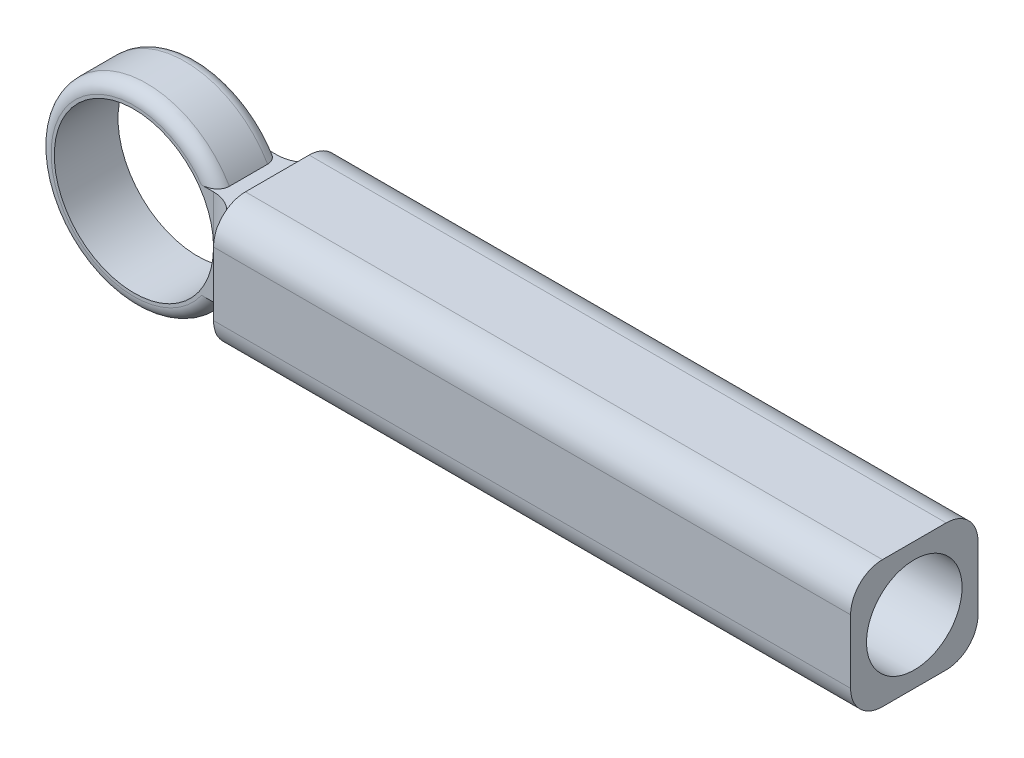
SolidWorks part; units mm, degrees
ref_plane "Plan de face" through (0, 0, 0) normal (0, 0, 1) x (1, 0, 0)
ref_plane "Plan de dessus" through (0, 0, 0) normal (0, 1, 0) x (1, 0, 0)
ref_plane "Plan de droite" through (0, 0, 0) normal (1, 0, 0) x (0, 0, -1)
sketch "Esquisse1" plane through (0, 0, 0) normal (0, 0, 1) x (1, 0, 0)
  line L0 (0, 0) -> (3.5, 0) construction
  line L2 (2.5981, 1.5) -> (3.5, 1.5)
  line L3 (3.5, 1.5) -> (3.5, -1.5)
  line L4 (3.5, -1.5) -> (2.5981, -1.5)
  arc A0 (2.5981, 1.5) -> (2.5981, -1.5) centre (0, 0) ccw
  circle A1 centre (0, 0) radius 2.5
  dimension "D1" = 5
  dimension "D2" = 6
  dimension "D3" = 3.5
  dimension "D4" = 3
extrude "Boss.-Extru.1" add sketch "Esquisse1" along normal blind 2
sketch "Esquisse2" plane through (3.5, 0, 0) normal (1, 0, 0) x (0, 0, -1)
  line L0 (0, 0) -> (-2, 0) construction
  line L2 (-2, -1.5) -> (-2, 1.5) construction
  line L8 (-3, -2) -> (1, -2)
  line L9 (-3, -2) -> (-3, 2)
  line L10 (-3, 2) -> (1, 2)
  line L11 (1, -2) -> (1, 2)
  line L12 (-3, -2) -> (1, 2) construction
  line L13 (-3, 2) -> (1, -2) construction
  point P6 (-1, 0)
  dimension "D1" = 4
  dimension "D2" = 4
extrude "Boss.-Extru.2" add sketch "Esquisse2" along normal blind 20 contours L9 L8 L11 L10
sketch "Esquisse3" plane through (23.5, 0, 0) normal (1, 0, 0) x (0, 0, -1)
  circle A0 centre (-1, 0) radius 1.5
  dimension "D1" = 3
extrude "Enlèv. mat.-Extru.2" cut sketch "Esquisse3" against normal blind 18.5
fillet "Congé1" radius 1 6 edges at (13.5, -2, 3) (13.5, -2, -1) (13.5, 2, -1) (13.5, 2, 3) (3.5, 0, 0) (3.5, 0, 2)
fillet "Congé2" radius 0.4 2 edges at (-3, 0, 2) (-3, 0, 0)
ref_plane "Plan1" through (0, 0, 1) normal (0, 0, 1) x (1, 0, 0)
sketch "Esquisse4" plane through (0, 0, 1) normal (0, 0, 1) x (1, 0, 0)
  circle A0 centre (0, 0) radius 2.5 construction
  circle A2 centre (0, 0) radius 2.5 construction
